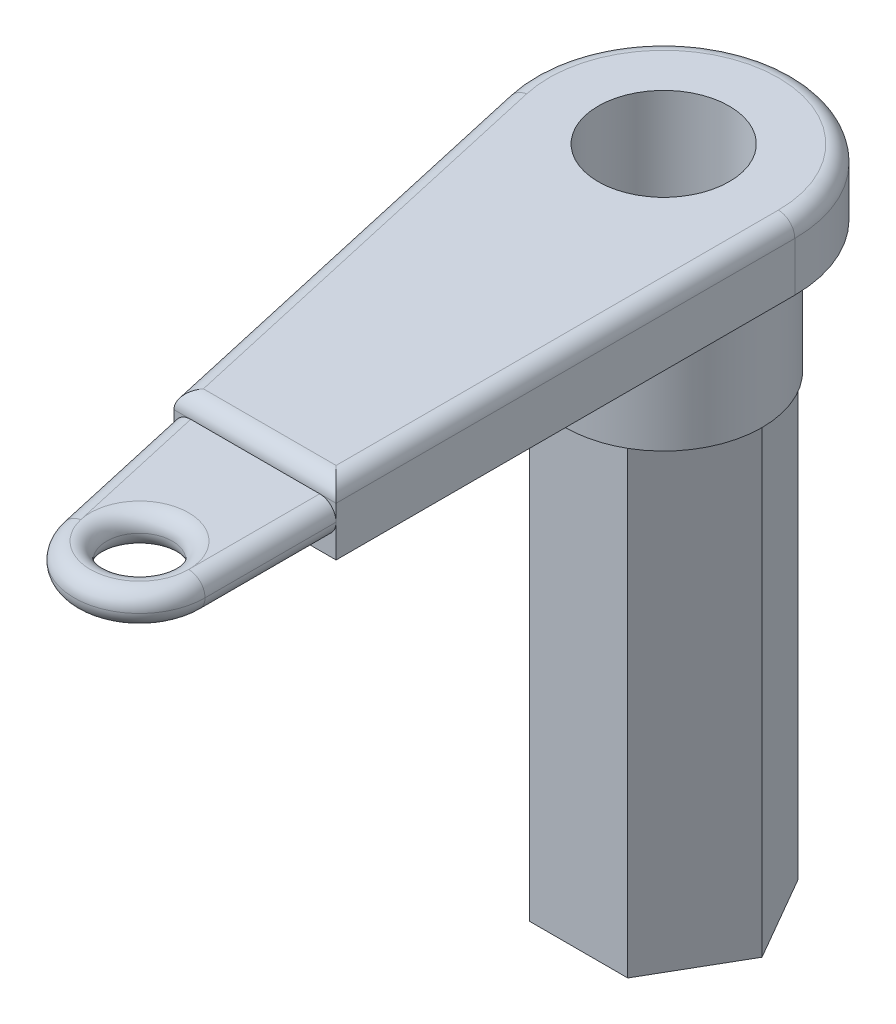
SolidWorks part; units mm, degrees
ref_plane "Front Plane" through (0, 0, 0) normal (0, 0, 1) x (1, 0, 0)
ref_plane "Top Plane" through (0, 0, 0) normal (0, 1, 0) x (1, 0, 0)
ref_plane "Right Plane" through (0, 0, 0) normal (1, 0, 0) x (0, 0, -1)
sketch "Sketch1" plane through (0, 0, 0) normal (0, 1, 0) x (1, 0, 0)
  line L0 (0, 20) -> (0, -90) construction
  line L1 (20, 0) -> (20, -90)
  line L2 (0, -90) -> (20, -90) construction
  line L3 (-19.5122, -4.3902) -> (0.2439, -92.1951)
  line L4 (0, -91.1111) -> (0, -100) construction
  arc A0 (20, 0) -> (-19.5122, -4.3902) centre (0, 0) ccw
  arc A2 (0.2439, -92.1951) -> (20, -90) centre (10, -90) ccw
  circle A3 centre (0, 0) radius 10
  circle A4 centre (10, -90) radius 5
  dimension "D1" = 120
  dimension "D2" = 40
  dimension "D4" = 20
  dimension "D3" = 10
extrude "Boss-Extrude2" add sketch "Sketch1" along normal blind 10
sketch "Sketch3" plane through (20, 0, 0) normal (1, 0, 0) x (0, 0, -1)
  line L0 (-100, 5) -> (-81.1129, 5) construction
  line L1 (-100, 10) -> (-70, 10)
  line L2 (-100, 10) -> (-100, 7.5)
  line L3 (-100, 7.5) -> (-70, 7.5)
  line L4 (-70, 10) -> (-70, 7.5)
  line L5 (-100, 10) -> (-100, 0) construction
  line L6 (-100, 0) -> (-100, 2.5)
  line L7 (-70, 0) -> (-70, 2.5)
  line L8 (-100, 2.5) -> (-70, 2.5)
  line L9 (-100, 0) -> (-70, 0)
  dimension "D1" = 2.5
  dimension "D2" = 30
extrude "Cut-Extrude3" cut sketch "Sketch3" against normal blind 32
fillet "Fillet1" radius 2.5 8 edges at (-2.253, 2.5, 81.0976) (20, 2.5, 80) (-2.253, 7.5, 81.0976) (11.1043, 7.5, 99.9388) (10, 2.5, 95) (11.1043, 2.5, 99.9388) (20, 7.5, 80) (10, 7.5, 85)
sketch "Sketch4" plane through (0, 0, 0) normal (0, -1, 0) x (1, 0, 0)
  circle A0 centre (0, 0) radius 15
  circle A1 centre (0, 0) radius 10
extrude "Boss-Extrude3" add sketch "Sketch4" along normal blind 20
sketch "Sketch5" plane through (0, -20, 0) normal (0, -1, 0) x (1, 0, 0)
  line L0 (0, 0) -> (38.0521, 0) construction
  line L1 (15, 0) -> (7.5, 12.9904)
  line L2 (7.5, 12.9904) -> (-7.5, 12.9904)
  line L3 (-7.5, 12.9904) -> (-15, 0)
  line L4 (-15, 0) -> (-7.5, -12.9904)
  line L5 (-7.5, -12.9904) -> (7.5, -12.9904)
  line L6 (7.5, -12.9904) -> (15, 0)
  circle A0 centre (0, 0) radius 12.9904 construction
  circle A1 centre (0, 0) radius 10
  dimension "D1" = 15
extrude "Boss-Extrude4" add sketch "Sketch5" along normal blind 70 contours L1 L2 L3 L4 L5 L6 | A1
fillet "Fillet2" radius 2.5 4 edges at (20, 10, 35) (-2.2086, 10, -19.8777) (7.625, 10, 70) (-12.1311, 10, 37.1951)
